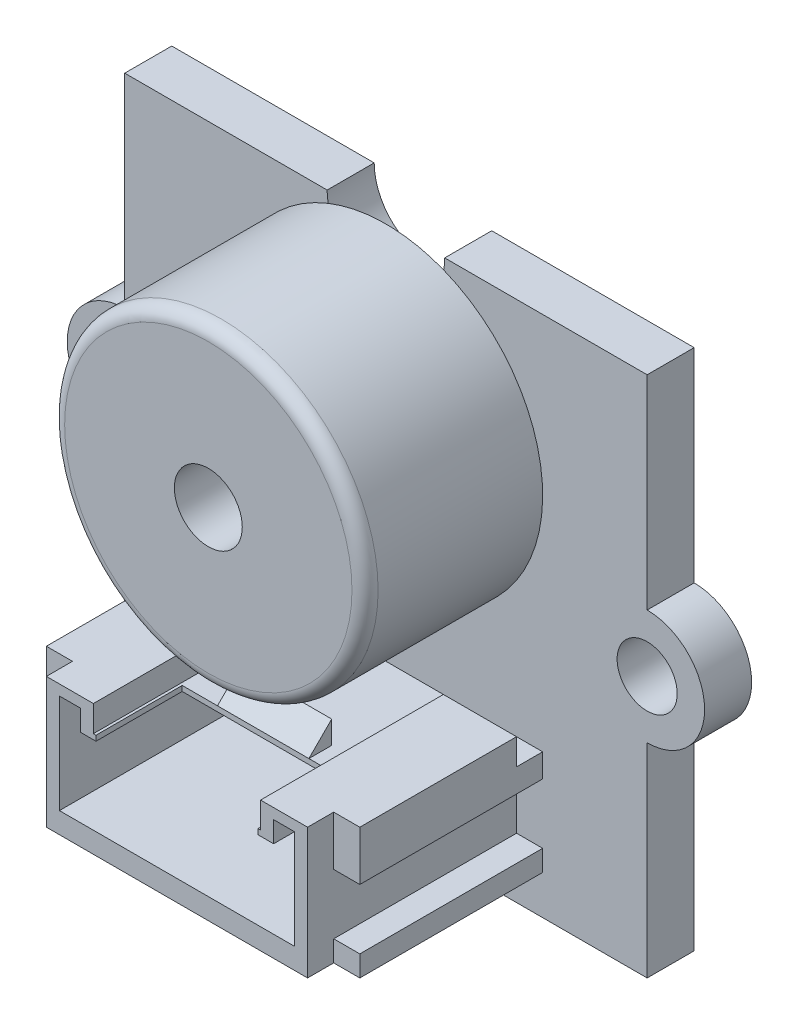
SolidWorks part; units mm, degrees
ref_plane "Plan de face" through (0, 0, 0) normal (0, 0, 1) x (1, 0, 0)
ref_plane "Plan de dessus" through (0, 0, 0) normal (0, 1, 0) x (1, 0, 0)
ref_plane "Plan de droite" through (0, 0, 0) normal (1, 0, 0) x (0, 0, -1)
sketch "Esquisse1" plane through (0, 0, 0) normal (0, 0, 1) x (1, 0, 0)
  line L0 (-2.7446, 10.9929) -> (-2.7446, -9.0071) construction
  line L1 (-12.7446, 10.9929) -> (-4.9946, 10.9929)
  line L2 (-12.7446, 10.9929) -> (-12.7446, 3.1929)
  line L3 (-12.7446, -9.0071) -> (-4.9946, -9.0071)
  line L4 (7.2554, 10.9929) -> (7.2554, 3.1929)
  line L5 (-12.7446, 0.9929) -> (7.2554, 0.9929) construction
  line L6 (-0.4946, 10.9929) -> (7.2554, 10.9929)
  line L7 (-0.4946, -9.0071) -> (7.2554, -9.0071)
  line L8 (-12.7446, -1.2071) -> (-12.7446, -9.0071)
  line L9 (7.2554, -1.2071) -> (7.2554, -9.0071)
  arc A0 (-4.9946, 10.9929) -> (-0.4946, 10.9929) centre (-2.7446, 10.9929) ccw
  arc A1 (-0.4946, -9.0071) -> (-4.9946, -9.0071) centre (-2.7446, -9.0071) ccw
  arc A2 (-12.7446, 3.1929) -> (-12.7446, -1.2071) centre (-12.7446, 0.9929) ccw
  arc A3 (7.2554, -1.2071) -> (7.2554, 3.1929) centre (7.2554, 0.9929) ccw
  circle A4 centre (-12.7446, 0.9929) radius 1.15
  circle A5 centre (7.2554, 0.9929) radius 1.15
  dimension "D1" = 20
  dimension "D2" = 20
extrude "Boss.-Extru.1" add sketch "Esquisse1" along normal blind 1.8
sketch "Esquisse2" plane through (0, 0, 1.8) normal (0, 0, 1) x (1, 0, 0)
  line L0 (-12.7446, -1.2071) -> (-12.7446, -9.0071) construction
  line L1 (-8.7446, -7.5071) -> (3.2554, -7.5071)
  line L2 (-8.7446, -7.5071) -> (-8.7446, -6.7071)
  line L3 (-8.7446, -2.5071) -> (3.2554, -2.5071)
  line L4 (3.2554, -7.5071) -> (3.2554, -6.7071)
  line L5 (-12.7446, -9.0071) -> (-4.9946, -9.0071) construction
  line L6 (3.2554, -4.4071) -> (2.2554, -4.4071)
  line L7 (-8.7446, -4.4071) -> (-7.7446, -4.4071)
  line L9 (-8.7446, -6.7071) -> (-7.7446, -6.7071)
  line L10 (-7.7446, -4.4071) -> (-7.7446, -6.7071)
  line L11 (2.2554, -4.4071) -> (2.2554, -6.7071)
  line L12 (2.2554, -6.7071) -> (3.2554, -6.7071)
  line L13 (-8.7446, -4.4071) -> (-8.7446, -2.5071)
  line L14 (3.2554, -4.4071) -> (3.2554, -2.5071)
  dimension "D1" = 12
  dimension "D2" = 5
  dimension "D3" = 4
  dimension "D4" = 1.5
  dimension "D5" = 1.9
  dimension "D6" = 1
  dimension "D7" = 2.3
extrude "Boss.-Extru.2" add sketch "Esquisse2" along normal blind 8
sketch "Esquisse3" plane through (0, 0, 9.8) normal (0, 0, 1) x (1, 0, 0)
  line L0 (-8.7446, -7.5071) -> (3.2554, -7.5071) construction
  line L1 (-6.4446, -3.7071) -> (0.9554, -3.7071)
  line L2 (-7.2446, -3.7071) -> (-7.2446, -6.7071)
  line L3 (-7.2446, -6.7071) -> (1.7554, -6.7071)
  line L4 (1.7554, -3.7071) -> (1.7554, -6.7071)
  line L5 (-7.7446, -4.4071) -> (-7.7446, -6.7071) construction
  line L6 (-7.2446, -3.7071) -> (-7.2446, -2.9071)
  line L7 (-7.2446, -2.9071) -> (-6.4446, -2.9071)
  line L8 (-6.4446, -2.9071) -> (-6.4446, -3.7071)
  line L9 (1.7554, -3.7071) -> (1.7554, -2.9071)
  line L10 (1.7554, -2.9071) -> (0.9554, -2.9071)
  line L11 (0.9554, -2.9071) -> (0.9554, -3.7071)
  dimension "D1" = 3
  dimension "D2" = 0.8
  dimension "D3" = 9
  dimension "D4" = 0.5
extrude "Enlèv. mat.-Extru.1" cut sketch "Esquisse3" against normal blind 7
sketch "Esquisse4" plane through (0, -2.5071, 0) normal (0, 1, 0) x (1, 0, 0)
  line L0 (-8.7446, -1.8) -> (3.2554, -1.8)
  line L1 (3.2554, -1.8) -> (3.2554, -2.8)
  line L2 (3.2554, -9.8) -> (3.2554, -1.8) construction
  line L3 (3.2554, -2.8) -> (0.4554, -2.8)
  line L4 (-8.7446, -1.8) -> (-8.7446, -2.8)
  line L5 (-8.7446, -9.8) -> (-8.7446, -1.8) construction
  line L6 (-8.7446, -2.8) -> (-5.9446, -2.8)
  line L7 (-5.9446, -2.8) -> (-5.9446, -9.8)
  line L8 (3.2554, -9.8) -> (-8.7446, -9.8) construction
  line L9 (0.4554, -2.8) -> (0.4554, -9.8)
  line L10 (0.4554, -9.8) -> (-5.9446, -9.8)
  line L11 (-2.7446, -9.8) -> (-2.7446, -3.7286) construction
  line L13 (-4.4946, -5.6264) -> (-0.9946, -5.6264)
  line L14 (-4.4946, -5.6264) -> (-4.4946, -6.5)
  line L15 (-4.4946, -6.5) -> (-0.9946, -6.5)
  line L16 (-0.9946, -5.6264) -> (-0.9946, -6.5)
  point P22 (-4.4946, -6.0632)
  dimension "D1" = 3.3
  dimension "D2" = 3.5
  dimension "D3" = 1.75
  dimension "D4" = 2.8
  dimension "D5" = 2.8
extrude "Enlèv. mat.-Extru.2" cut sketch "Esquisse4" against normal blind 1
sketch "Esquisse5" plane through (0, -2.5071, 0) normal (0, 1, 0) x (1, 0, 0)
  line L0 (-8.7446, -9.8) -> (-8.7446, -2.8) construction
  line L1 (-8.7446, -9.8) -> (-7.7446, -9.8)
  line L2 (-8.7446, -9.8) -> (-8.7446, -8.8)
  line L3 (-8.7446, -8.8) -> (-7.7446, -8.8)
  line L4 (-7.7446, -9.8) -> (-7.7446, -8.8)
  line L5 (-5.9446, -9.8) -> (-8.7446, -9.8) construction
  line L7 (3.2554, -9.8) -> (2.2554, -9.8)
  line L8 (3.2554, -9.8) -> (3.2554, -8.8)
  line L9 (3.2554, -8.8) -> (2.2554, -8.8)
  line L10 (2.2554, -9.8) -> (2.2554, -8.8)
  dimension "D1" = 1
  dimension "D2" = 1
  dimension "D3" = 1
extrude "Enlèv. mat.-Extru.3" cut sketch "Esquisse5" against normal blind 11
sketch "Esquisse6" plane through (0, -3.5071, 0) normal (0, 1, 0) x (1, 0, 0)
  line L0 (-5.9446, -9.8) -> (0.4554, -9.8) construction
  line L1 (-5.8446, -9.8) -> (0.3554, -9.8)
  line L2 (-5.8446, -9.8) -> (-5.8446, -6.5)
  line L3 (-5.8446, -6.5) -> (0.3554, -6.5)
  line L4 (0.3554, -9.8) -> (0.3554, -6.5)
  line L5 (-8.7446, -8.8) -> (-8.7446, -2.8) construction
  dimension "D1" = 6.2
  dimension "D2" = 2.9
  dimension "D3" = 3.3
extrude "Enlèv. mat.-Extru.4" cut sketch "Esquisse6" against normal blind 1
chamfer "Chanfrein1" distance 1 angle 45 1 edges at (-2.7446, -2.5071, 6.5)
sketch "Esquisse7" plane through (0, 0, 1.8) normal (0, 0, 1) x (1, 0, 0)
  line L0 (-12.7446, 4.9929) -> (7.2554, 4.9929) construction
  line L1 (-12.7446, 10.9929) -> (-12.7446, 3.1929) construction
  line L2 (7.2554, 3.1929) -> (7.2554, 10.9929) construction
  line L3 (-4.9946, 10.9929) -> (-12.7446, 10.9929) construction
  circle A0 centre (-2.7446, 4.9929) radius 6
  dimension "D1" = 6
extrude "Boss.-Extru.3" add sketch "Esquisse7" along normal blind 6.8
fillet "Congé1" radius 0.5 1 edges at (3.2554, 4.9929, 8.6)
sketch "Esquisse8" plane through (0, 0, 8.6) normal (0, 0, 1) x (1, 0, 0)
  circle A0 centre (-2.7446, 4.9929) radius 1.3
extrude "Enlèv. mat.-Extru.5" cut sketch "Esquisse8" against normal blind 2
